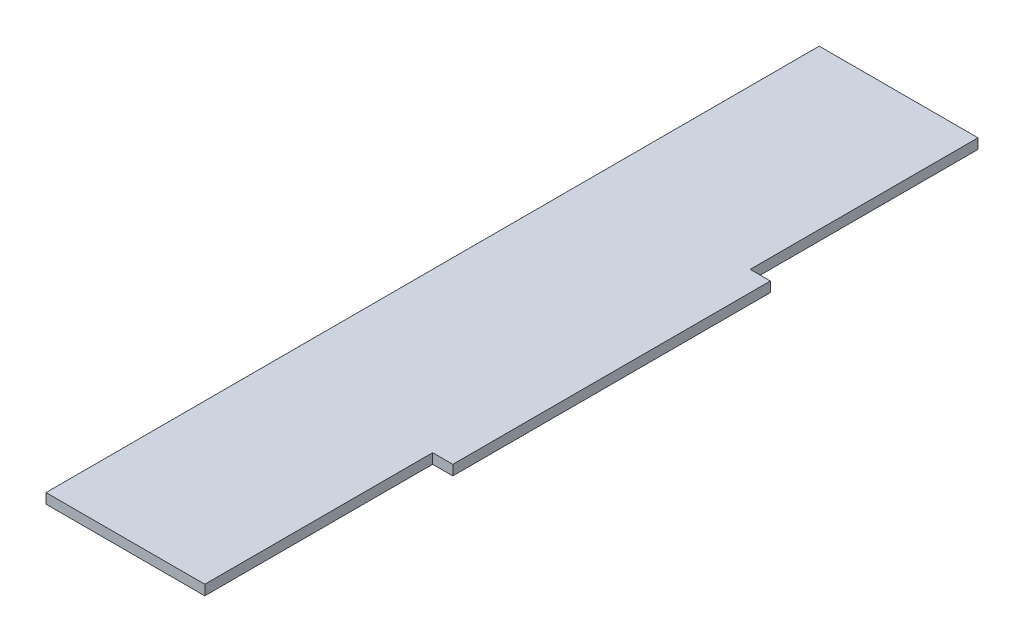
SolidWorks part; units mm, degrees
ref_plane "Front Plane" through (0, 0, 0) normal (0, 0, 1) x (1, 0, 0)
ref_plane "Top Plane" through (0, 0, 0) normal (0, 1, 0) x (1, 0, 0)
ref_plane "Right Plane" through (0, 0, 0) normal (1, 0, 0) x (0, 0, -1)
sketch "Sketch1" plane through (0, 0, 0) normal (0, 1, 0) x (1, 0, 0)
  line L0 (-25, 71.75) -> (25, 71.75)
  line L1 (25, 71.75) -> (25, 0)
  line L2 (25, 0) -> (31.35, 0)
  line L3 (31.35, 0) -> (31.35, -100)
  line L4 (31.35, -100) -> (25, -100)
  line L5 (25, -100) -> (25, -171.75)
  line L6 (25, -171.75) -> (-25, -171.75)
  line L7 (-25, -171.75) -> (-25, -100)
  line L8 (-25, -100) -> (-31.35, -100)
  line L9 (-31.35, -100) -> (-31.35, 0)
  line L10 (-31.35, 0) -> (-25, 0)
  line L11 (-25, 0) -> (-25, 71.75)
  line L12 (-25, 0) -> (-25, -100) construction
  point P11 (0, 71.75)
  point P14 (-31.35, -50)
  dimension "D1" = 6.35
  dimension "D2" = 100
  dimension "D3" = 50
  dimension "D4" = 243.5
extrude "Boss-Extrude1" add sketch "Sketch1" along normal blind 3.175 contours L11 L12 L7 L6 L5 L4 L3 L2 L1 L0 region at (1.3967, 0, 50)
equation "\"length\" = 243.5mm"
equation "\"w_mach\" = 50mm"
equation "\"w_tab\"= 100mm"
equation "\"t_wood\"= 0.125in"
equation "\"t_side\"= 0.25in"
equation "\"D1@Sketch1\"=\"t_side\""
equation "\"D2@Sketch1\"=\"w_tab\""
equation "\"D3@Sketch1\"=\"w_mach\""
equation "\"D4@Sketch1\"=\"length\""
equation "\"D1@Boss-Extrude1\"=\"t_wood\""
